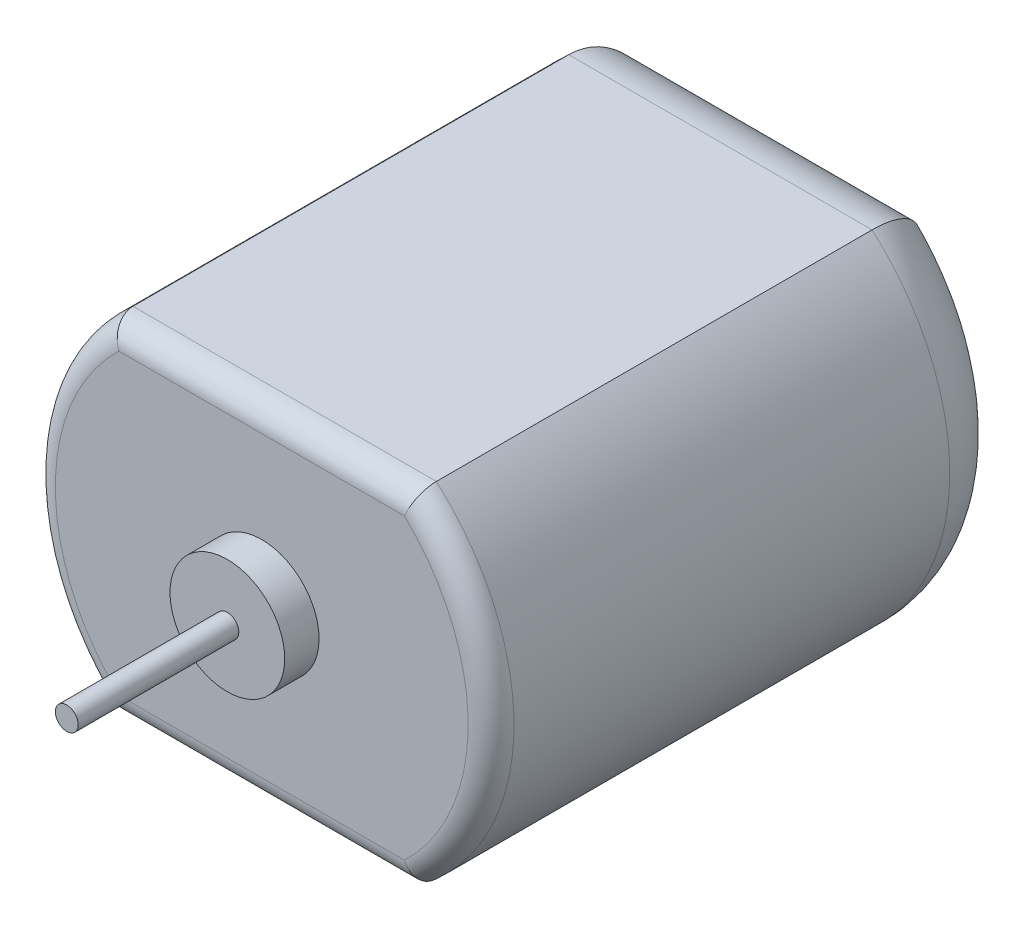
SolidWorks part; units mm, degrees
ref_plane "Front Plane" through (0, 0, 0) normal (0, 0, 1) x (1, 0, 0)
ref_plane "Top Plane" through (0, 0, 0) normal (0, 1, 0) x (1, 0, 0)
ref_plane "Right Plane" through (0, 0, 0) normal (1, 0, 0) x (0, 0, -1)
sketch "Sketch1" plane through (0, 0, 0) normal (0, 0, 1) x (1, 0, 0)
  line L0 (-6.6144, 7.5) -> (6.6144, 7.5)
  line L1 (6.6144, 7.5) -> (6.6144, -7.5) construction
  line L2 (6.6144, -7.5) -> (-6.6144, -7.5)
  arc A0 (-6.6144, 7.5) -> (-6.6144, -7.5) centre (0, 0) ccw
  arc A1 (6.6144, -7.5) -> (6.6144, 7.5) centre (0, 0) ccw
  dimension "D1" = 20
  dimension "D2" = 15
extrude "Boss-Extrude1" add sketch "Sketch1" along normal blind 23
sketch "Sketch2" plane through (0, 0, 23) normal (0, 0, 1) x (1, 0, 0)
  circle A0 centre (0, 0) radius 2.5
  dimension "D1" = 5
extrude "Boss-Extrude2" add sketch "Sketch2" along normal blind 1.5
sketch "Sketch3" plane through (0, 0, 24.5) normal (0, 0, 1) x (1, 0, 0)
  circle A0 centre (0, 0) radius 0.5
  dimension "D1" = 1
extrude "Boss-Extrude3" add sketch "Sketch3" along normal blind 7
fillet "Fillet1" radius 1 4 edges at (-10, 0, 23) (0, -7.5, 23) (10, 0, 23) (0, 7.5, 23)
fillet "Fillet2" radius 3 4 edges at (0, -7.5, 0) (10, 0, 0) (0, 7.5, 0) (-10, 0, 0)
sketch "Sketch4" plane through (0, 0, 0) normal (0, 0, -1) x (-1, 0, 0)
  line L0 (-2.7586, 1.6066) -> (2.7586, 1.6066)
  arc A0 (-2.7586, 1.6066) -> (2.7586, 1.6066) centre (0, 0) ccw
extrude "Boss-Extrude4" add sketch "Sketch4" along normal blind 1
fillet "Fillet3" radius 0.5 2 edges at (0, 1.6066, -1) (0, -3.1923, -1)
